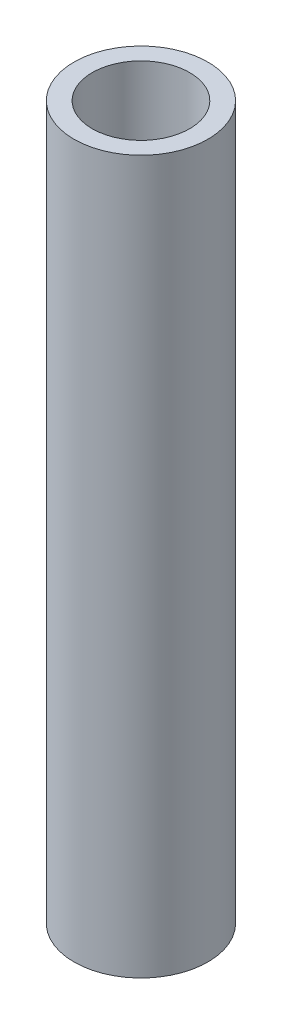
SolidWorks part; units mm, degrees
ref_plane "Front Plane" through (0, 0, 0) normal (0, 0, 1) x (1, 0, 0)
ref_plane "Top Plane" through (0, 0, 0) normal (0, 1, 0) x (1, 0, 0)
ref_plane "Right Plane" through (0, 0, 0) normal (1, 0, 0) x (0, 0, -1)
sketch "Sketch1" plane through (0, 0, 0) normal (0, 1, 0) x (1, 0, 0)
  circle A0 centre (0, 0) radius 12.1539
  circle A1 centre (0, 0) radius 16.7005
  dimension "D1" = 24.3078
  dimension "D2" = 33.401
extrude "Boss-Extrude1" add sketch "Sketch1" along normal mid plane 177.8
